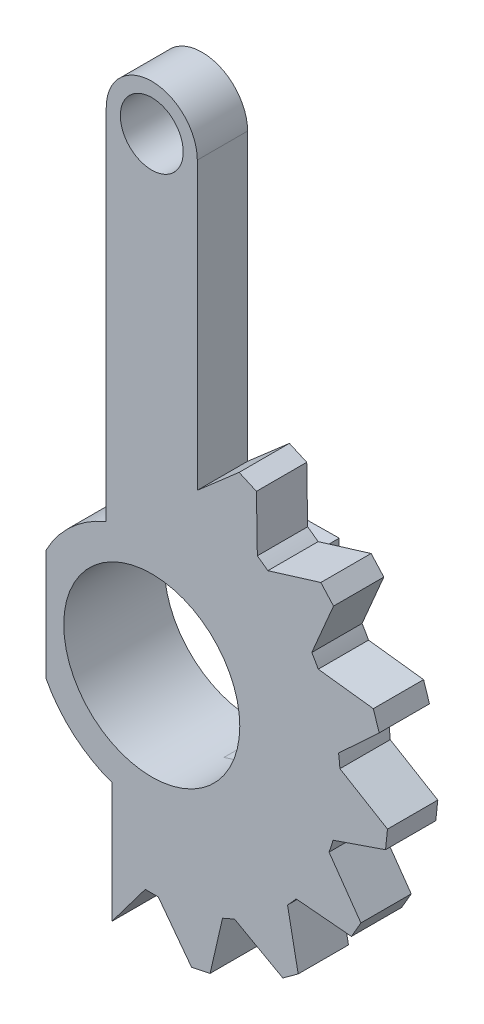
SolidWorks part; units mm, degrees
note: The reader was unsure of these and kept them because the rebuilt part matched: shared geometry of "Sketch1<4>".
ref_plane "Front Plane" through (0, 0, 0) normal (0, 0, 1) x (1, 0, 0)
ref_plane "Top Plane" through (0, 0, 0) normal (0, 1, 0) x (1, 0, 0)
ref_plane "Right Plane" through (0, 0, 0) normal (1, 0, 0) x (0, 0, -1)
sketch "Sketch1" plane through (0, 0, 0) normal (0, 0, 1) x (1, 0, 0)
  line L0 (0, 0) -> (0, 5476.8163) construction
  line L1 (0, 0) -> (-5476.8163, 0) construction
  line L3 (-1.3065, 7.3853) -> (-0.3773, 9.3853)
  line L4 (1.3065, 7.3853) -> (0.3773, 9.3853)
  line L5 (-0.3773, 9.3853) -> (0.3773, 9.3853)
  line L6 (4.1974, 6.2154) -> (4.162, 8.4205)
  line L7 (3.4727, 8.7274) -> (4.162, 8.4205)
  line L8 (1.8103, 7.2782) -> (3.4727, 8.7274)
  line L9 (6.3626, 3.9708) -> (7.2271, 5.9996)
  line L10 (6.7222, 6.5604) -> (7.2271, 5.9996)
  line L11 (4.6142, 5.9127) -> (6.7222, 6.5604)
  line L12 (7.4276, 1.0396) -> (9.0426, 2.5414)
  line L13 (8.8094, 3.2591) -> (9.0426, 2.5414)
  line L14 (6.6201, 3.5247) -> (8.8094, 3.2591)
  line L15 (7.2083, -2.0713) -> (9.2945, -1.3563)
  line L16 (9.3734, -0.6058) -> (9.2945, -1.3563)
  line L17 (7.4814, 0.5274) -> (9.3734, -0.6058)
  line L18 (5.7426, -4.8241) -> (7.9393, -5.0194)
  line L19 (8.3166, -4.3659) -> (7.9393, -5.0194)
  line L20 (7.0491, -2.5612) -> (8.3166, -4.3659)
  line L21 (3.284, -6.7428) -> (5.2113, -7.8147)
  line L22 (5.8218, -7.3711) -> (5.2113, -7.8147)
  line L23 (5.398, -5.2069) -> (5.8218, -7.3711)
  line L24 (0.2576, -7.4956) -> (1.5823, -9.2587)
  line L25 (2.3204, -9.1018) -> (1.5823, -9.2587)
  line L26 (2.8134, -6.9523) -> (2.3204, -9.1018)
  line L27 (-2.8134, -6.9523) -> (-2.3204, -9.1018)
  line L28 (-1.5823, -9.2587) -> (-2.3204, -9.1018)
  line L29 (-0.2576, -7.4956) -> (-1.5823, -9.2587)
  line L30 (-5.398, -5.2069) -> (-5.8218, -7.3711)
  line L31 (-5.2113, -7.8147) -> (-5.8218, -7.3711)
  line L32 (-3.284, -6.7428) -> (-5.2113, -7.8147)
  line L33 (-7.0491, -2.5612) -> (-8.3166, -4.3659)
  line L34 (-7.9393, -5.0194) -> (-8.3166, -4.3659)
  line L35 (-5.7426, -4.8241) -> (-7.9393, -5.0194)
  line L36 (-7.4814, 0.5274) -> (-9.3734, -0.6058)
  line L37 (-9.2945, -1.3563) -> (-9.3734, -0.6058)
  line L38 (-7.2083, -2.0713) -> (-9.2945, -1.3563)
  line L39 (-6.6201, 3.5247) -> (-8.8094, 3.2591)
  line L40 (-9.0426, 2.5414) -> (-8.8094, 3.2591)
  line L41 (-7.4276, 1.0396) -> (-9.0426, 2.5414)
  line L42 (-4.6142, 5.9127) -> (-6.7222, 6.5604)
  line L43 (-7.2271, 5.9996) -> (-6.7222, 6.5604)
  line L44 (-6.3626, 3.9708) -> (-7.2271, 5.9996)
  line L45 (-1.8103, 7.2782) -> (-3.4727, 8.7274)
  line L46 (-4.162, 8.4205) -> (-3.4727, 8.7274)
  line L47 (-4.1974, 6.2154) -> (-4.162, 8.4205)
  line L48 (1.8103, 7.2782) -> (1.8103, 18.65)
  line L49 (-1.8103, 18.65) -> (-1.8103, 4.3915)
  line L50 (-1.5823, -4.4787) -> (-1.5823, -9.2587)
  line L51 (-4.1974, 2.2235) -> (-4.1974, -2.2235)
  line L52 (-1.8103, 4.3915) -> (3.4546, 4.4535)
  line L53 (3.4546, 4.4535) -> (3.3394, 2.7574)
  line L54 (3.3394, 2.7574) -> (0.8688, 3.3905)
  line L55 (0.8688, 3.3905) -> (0.8967, 3.3832)
  line L56 (3.4546, -4.4535) -> (3.3394, -2.7574)
  line L57 (-1.8103, -4.3915) -> (3.4546, -4.4535)
  line L58 (3.3394, -2.7574) -> (0.8688, -3.3905)
  arc A0 (-1.3065, 7.3853) -> (-1.8103, 7.2782) centre (0, 0) ccw
  arc A1 (1.8103, 7.2782) -> (1.3065, 7.3853) centre (0, 0) ccw
  arc A2 (4.6142, 5.9127) -> (4.1974, 6.2154) centre (0, 0) ccw
  arc A3 (6.6201, 3.5247) -> (6.3626, 3.9708) centre (0, 0) ccw
  arc A4 (7.4814, 0.5274) -> (7.4276, 1.0396) centre (0, 0) ccw
  arc A5 (7.0491, -2.5612) -> (7.2083, -2.0713) centre (0, 0) ccw
  arc A6 (5.398, -5.2069) -> (5.7426, -4.8241) centre (0, 0) ccw
  arc A7 (2.8134, -6.9523) -> (3.284, -6.7428) centre (0, 0) ccw
  arc A8 (-0.2576, -7.4956) -> (0.2576, -7.4956) centre (0, 0) ccw
  arc A9 (-3.284, -6.7428) -> (-2.8134, -6.9523) centre (0, 0) ccw
  arc A10 (-5.7426, -4.8241) -> (-5.398, -5.2069) centre (0, 0) ccw
  arc A11 (-7.2083, -2.0713) -> (-7.0491, -2.5612) centre (0, 0) ccw
  arc A12 (-7.4276, 1.0396) -> (-7.4814, 0.5274) centre (0, 0) ccw
  arc A13 (-6.3626, 3.9708) -> (-6.6201, 3.5247) centre (0, 0) ccw
  arc A14 (-4.1974, 6.2154) -> (-4.6142, 5.9127) centre (0, 0) ccw
  circle A15 centre (0, 0) radius 3.5
  arc A16 (1.8103, 18.65) -> (-1.8103, 18.65) centre (0, 18.65) ccw
  circle A17 centre (0, 18.65) radius 1.25
  arc A18 (-1.8103, 4.3915) -> (-4.1974, 2.2235) centre (0, 0) ccw
  arc A19 (-4.1974, -2.2235) -> (-1.5823, -4.4787) centre (0, 0) ccw
  point P10 (0, 7.5)
  dimension "D1" = 15
  dimension "D4" = 7
  dimension "D5" = 2.5
  dimension "D6" = 9.5
  dimension "D2" = 15
  dimension "D3" = 2
  dimension "D7" = 1.7
  dimension "D8" = 18.65
extrude "Boss-Extrude2" add sketch "Sketch1" along normal blind 2 contours L57 A19 L50 L29 A8 L24 L25 L26 A7 L21 L22 L23 A6 L18 L19 L20 A5 L15 L16 L17 A4 L12 L13 L14 A3 L9 L10 L11 A2 L6 L7 L8 A1 L4 L5 L3 A0 L49 L52 L53 L54 A15 L58 L56 | L48 A16 L49 A0 L3 L5 L4 A1 A17 | L51 A19 L57 L56 L58 A15 L54 L53 L52 A18
extrude "Boss-Extrude3" add sketch "Sketch1<4>" along normal blind 3.5 from offset 2 contours L51 A19 L57 L56 L58 A15 L54 L53 L52 A18
sketch "Sketch1<4>" plane through (0, 0, 0) normal (0, 0, 1) x (1, 0, 0) same geometry as "Sketch1"
